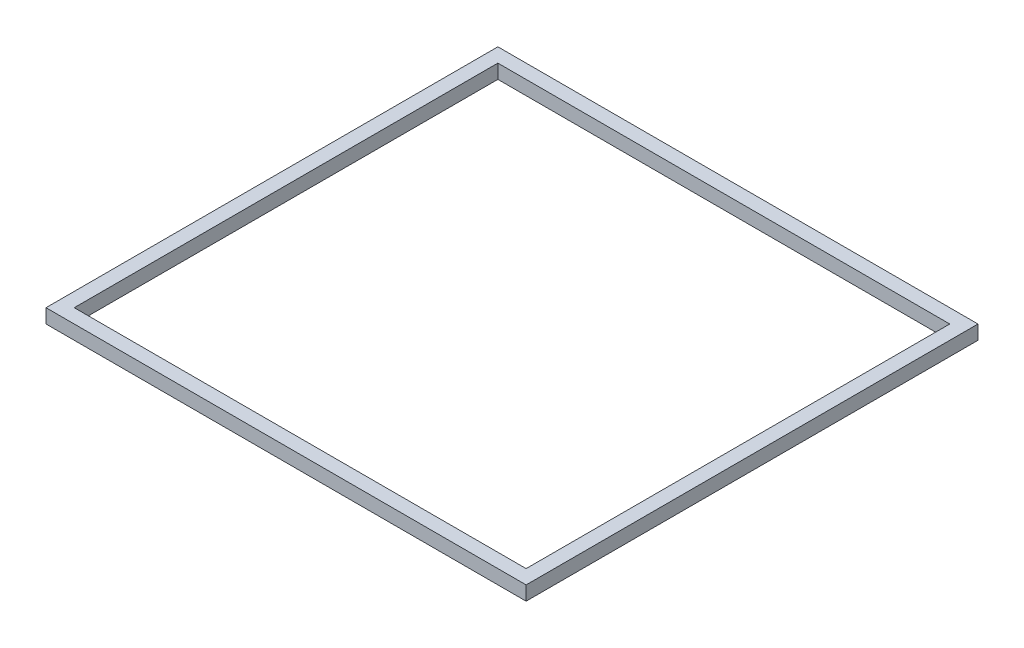
SolidWorks part; units mm, degrees
material "6061 合金"
ref_plane "前视基准面" through (0, 0, 0) normal (0, 0, 1) x (1, 0, 0)
ref_plane "上视基准面" through (0, 0, 0) normal (0, 1, 0) x (1, 0, 0)
ref_plane "右视基准面" through (0, 0, 0) normal (1, 0, 0) x (0, 0, -1)
sketch "草图1" plane through (0, 0, 0) normal (0, 1, 0) x (1, 0, 0)
  line L1 (-329.3879, 147.905) -> (350.6121, 147.905)
  line L2 (-329.3879, 147.905) -> (-329.3879, -492.095)
  line L3 (-329.3879, -492.095) -> (350.6121, -492.095)
  line L4 (350.6121, 147.905) -> (350.6121, -492.095)
  line L5 (-309.3879, 127.905) -> (330.6121, 127.905)
  line L6 (-309.3879, 127.905) -> (-309.3879, -472.095)
  line L7 (-309.3879, -472.095) -> (330.6121, -472.095)
  line L8 (330.6121, 127.905) -> (330.6121, -472.095)
  dimension "D1" = 680
  dimension "D2" = 640
  dimension "D3" = 20
  dimension "D4" = 20
  dimension "D5" = 20
  dimension "D6" = 20
extrude "凸台-拉伸1" add sketch "草图1" along normal blind 20
